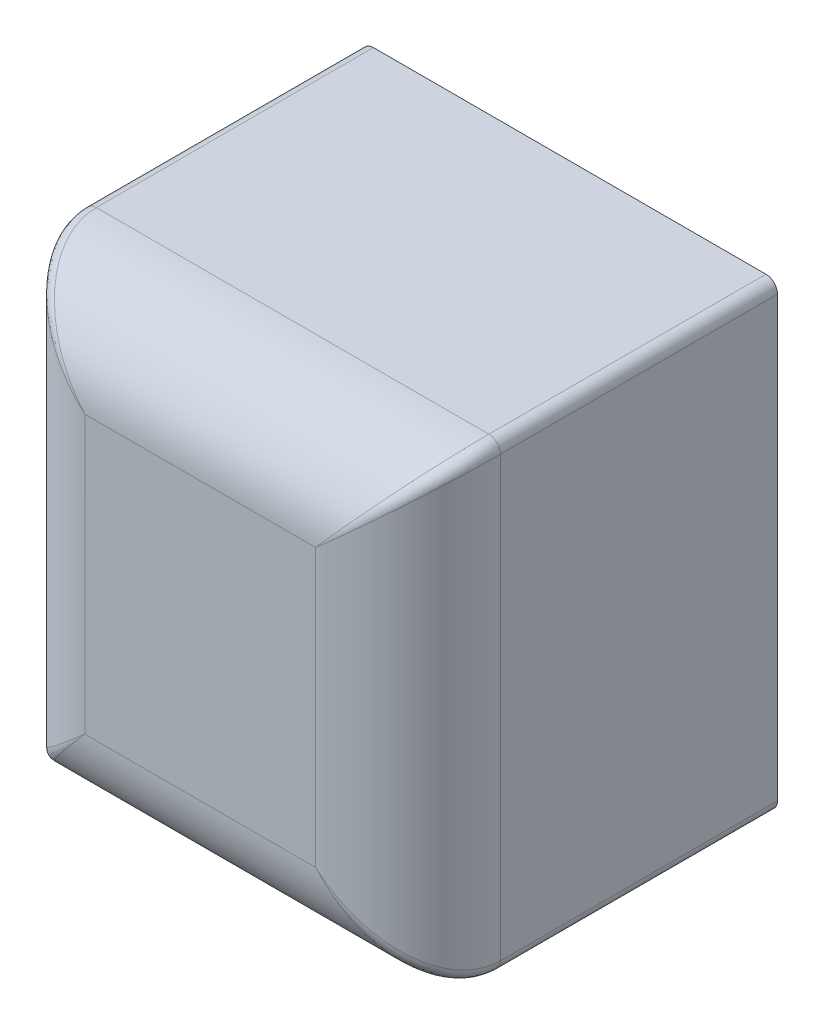
SolidWorks part; units mm, degrees
ref_plane "Front Plane" through (0, 0, 0) normal (0, 0, 1) x (1, 0, 0)
ref_plane "Top Plane" through (0, 0, 0) normal (0, 1, 0) x (1, 0, 0)
ref_plane "Right Plane" through (0, 0, 0) normal (1, 0, 0) x (0, 0, -1)
sketch "Sketch1" plane through (0, 0, 0) normal (0, 1, 0) x (1, 0, 0)
  line L1 (-90, -80) -> (90, -80)
  line L2 (-90, -80) -> (-90, 80)
  line L3 (-90, 80) -> (90, 80)
  line L4 (90, -80) -> (90, 80)
  line L5 (-90, -80) -> (90, 80) construction
  line L6 (-90, 80) -> (90, -80) construction
  point P0 (0, 0)
  dimension "D1" = 160
  dimension "D2" = 180
extrude "Boss-Extrude1" add sketch "Sketch1" along normal blind 200
fillet "Fillet1" radius 40 4 edges at (0, 200, 80) (0, 0, 80) (90, 100, 80) (-90, 100, 80)
fillet "Fillet2" radius 5 8 edges at (78.2843, 11.7157, 68.2843) (78.2843, 188.2843, 68.2843) (-78.2843, 188.2843, 68.2843) (-78.2843, 11.7157, 68.2843) (90, 0, -20) (90, 200, -20) (-90, 200, -20) (-90, 0, -20)
